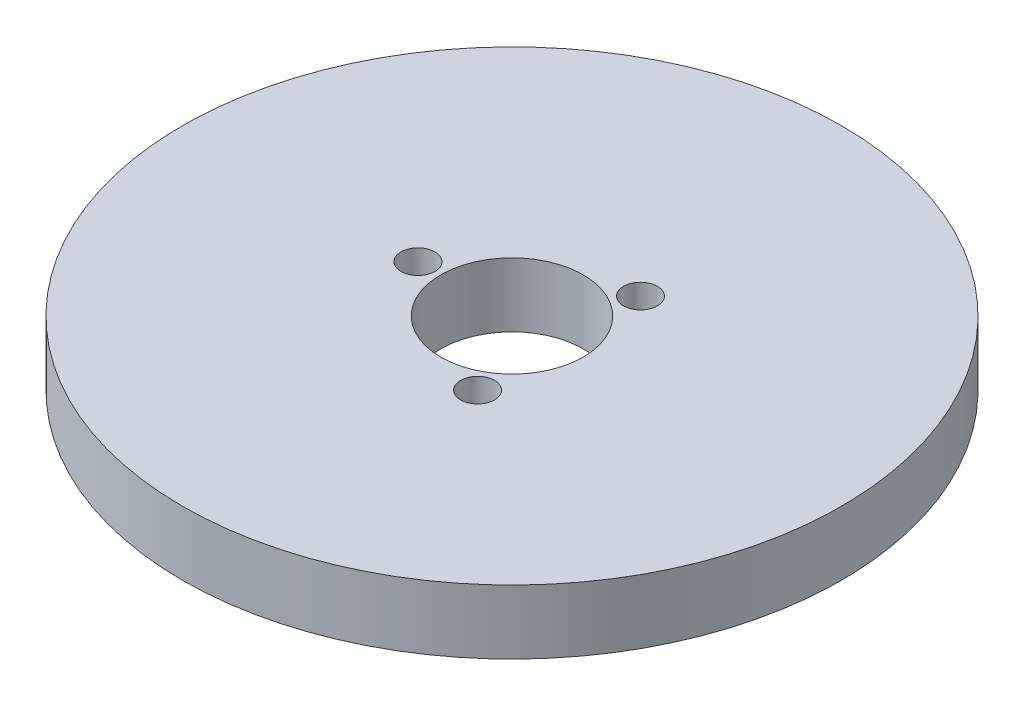
SolidWorks part; units mm, degrees
ref_plane "Front Plane" through (0, 0, 0) normal (0, 0, 1) x (1, 0, 0)
ref_plane "Top Plane" through (0, 0, 0) normal (0, 1, 0) x (1, 0, 0)
ref_plane "Right Plane" through (0, 0, 0) normal (1, 0, 0) x (0, 0, -1)
sketch "Sketch1" plane through (0, 0, 0) normal (0, 1, 0) x (1, 0, 0)
  circle A0 centre (0, 0) radius 92.5
  dimension "FLANGE_OD" = 185
extrude "Boss-Extrude1" add sketch "Sketch1" along normal blind 18
sketch "Sketch2" plane through (0, 0, 0) normal (0, 1, 0) x (1, 0, 0)
  circle A0 centre (0, 0) radius 20
  dimension "BORE_D" = 40
extrude "Cut-Extrude1" cut sketch "Sketch2" along normal through all
sketch "Sketch3" plane through (0, 18, 0) normal (0, 1, 0) x (1, 0, 0)
  circle A0 centre (0, 0) radius 26.3978 construction
  circle A1 centre (-26.3978, 0) radius 4.7631
  dimension "BOLT_D" = 9.5261
  dimension "BOLT_PCD" = 52.7956
extrude "Cut-Extrude2" cut sketch "Sketch3" against normal blind 17.7583
pattern_circular "CirPattern1" count 3 over 360 about axis through (0, 0, 0) along (0, 1, 0) of "Cut-Extrude2"
